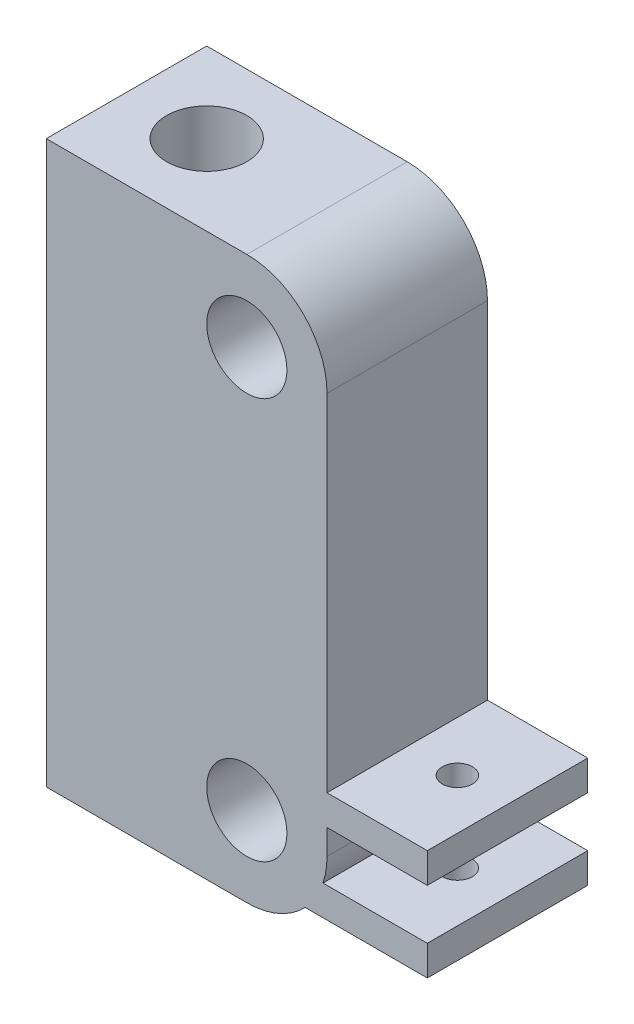
SolidWorks part; units mm, degrees
material "ABS"
ref_plane "Front Plane" through (0, 0, 0) normal (0, 0, 1) x (1, 0, 0)
ref_plane "Top Plane" through (0, 0, 0) normal (0, 1, 0) x (1, 0, 0)
ref_plane "Right Plane" through (0, 0, 0) normal (1, 0, 0) x (0, 0, -1)
sketch "Sketch1" plane through (0, 0, 0) normal (0, 0, 1) x (1, 0, 0)
  line L0 (11.942, -20.8688) -> (21.942, -20.8688)
  line L1 (-16.058, 21.6312) -> (3.942, 21.6312)
  line L2 (-16.058, 21.6312) -> (-16.058, -34.3688)
  line L3 (-16.058, -34.3688) -> (3.942, -34.3688)
  line L4 (11.942, 13.6312) -> (11.942, -20.8688)
  line L5 (21.942, -20.8688) -> (21.942, -23.8688)
  line L6 (21.942, -23.8688) -> (11.942, -23.8688)
  line L7 (9.7514, -31.8688) -> (21.942, -31.8688)
  line L8 (21.942, -31.8688) -> (21.942, -28.8688)
  line L9 (21.942, -28.8688) -> (11.5413, -28.8688)
  line L10 (11.942, -23.8688) -> (11.942, -26.3688)
  circle A0 centre (3.942, 13.6312) radius 4
  circle A1 centre (3.942, -26.3688) radius 4
  arc A2 (3.942, -34.3688) -> (9.7514, -31.8688) centre (3.942, -26.3688) ccw
  arc A3 (3.942, 21.6312) -> (11.942, 13.6312) centre (3.942, 13.6312) cw
  arc A4 (11.5413, -28.8688) -> (11.942, -26.3688) centre (3.942, -26.3688) ccw
  dimension "D1" = 8
  dimension "D2" = 8
  dimension "D8" = 8
  dimension "D3" = 40
  dimension "D4" = 8
  dimension "D5" = 8
  dimension "D6" = 8
  dimension "D7" = 8
  dimension "D9" = 28
  dimension "D10" = 3
  dimension "D11" = 3
  dimension "D12" = 2.5
  dimension "D13" = 5
  dimension "D14" = 10
extrude "Boss-Extrude1" add sketch "Sketch1" against normal blind 16
sketch "Sketch2" plane through (0, 21.6312, 0) normal (0, 1, 0) x (1, 0, 0)
  line L0 (3.942, 0) -> (-16.058, 0) construction
  line L1 (-16.058, 16) -> (-16.058, 0) construction
  circle A0 centre (-8.058, 8) radius 4
  dimension "D1" = 8
  dimension "D2" = 8
  dimension "D3" = 8
extrude "Cut-Extrude1" cut sketch "Sketch2" against normal through all
ref_point "Point1"
sketch "Sketch3" plane through (0, -20.8688, 0) normal (0, 1, 0) x (1, 0, 0)
  line L0 (21.942, 16) -> (21.942, 0) construction
  line L2 (21.942, 16) -> (11.942, 16) construction
  circle A0 centre (16.942, 8) radius 1.5
  dimension "D1" = 3
  dimension "D2" = 5
  dimension "D3" = 8
extrude "Cut-Extrude2" cut sketch "Sketch3" against normal through all
equation "\"rod_diameter\"= 8"
equation "\"rod_hole_thickness\"= 4"
equation "\"D1@Sketch1\"=\"rod_diameter\""
equation "\"D2@Sketch1\"=\"rod_diameter\""
equation "\"rod_radius\"= \"rod_diameter\" / 2"
equation "\"D4@Sketch1\"=\"rod_radius\"+\"rod_hole_thickness\""
equation "\"D5@Sketch1\"=\"rod_radius\"+\"rod_hole_thickness\""
equation "\"D6@Sketch1\"=\"rod_radius\"+\"rod_hole_thickness\""
equation "\"D7@Sketch1\"=\"rod_radius\"+\"rod_hole_thickness\""
equation "\"D8@Sketch1\"=\"rod_radius\"+\"rod_hole_thickness\""
equation "\"D9@Sketch1\"=\"rod_diameter\"*2 + \"rod_hole_thickness\"*3"
equation "\"D1@Boss-Extrude1\"= \"rod_diameter\" + \"rod_hole_thickness\" * 2"
equation "\"D1@Sketch2\"=\"rod_diameter\""
equation "\"D2@Sketch2\"=\"rod_radius\"+\"rod_hole_thickness\""
equation "\"D3@Sketch2\" = \"rod_radius\" + \"rod_hole_thickness\""
equation "\"platter_diameter\"= 320"
equation "\"platter_radius\"= \"platter_diameter\" / 2"
equation "\"extruder_mount_hole_spacing\"= 75"
equation "\"arm_rod_spacing\"= 40"
equation "\"D3@Sketch1\"=\"arm_rod_spacing\""
equation "\"D2@Sketch3\" = \"D14@Sketch1\" / 2"
equation "\"D3@Sketch3\"= \"D1@Boss-Extrude1\" / 2"
